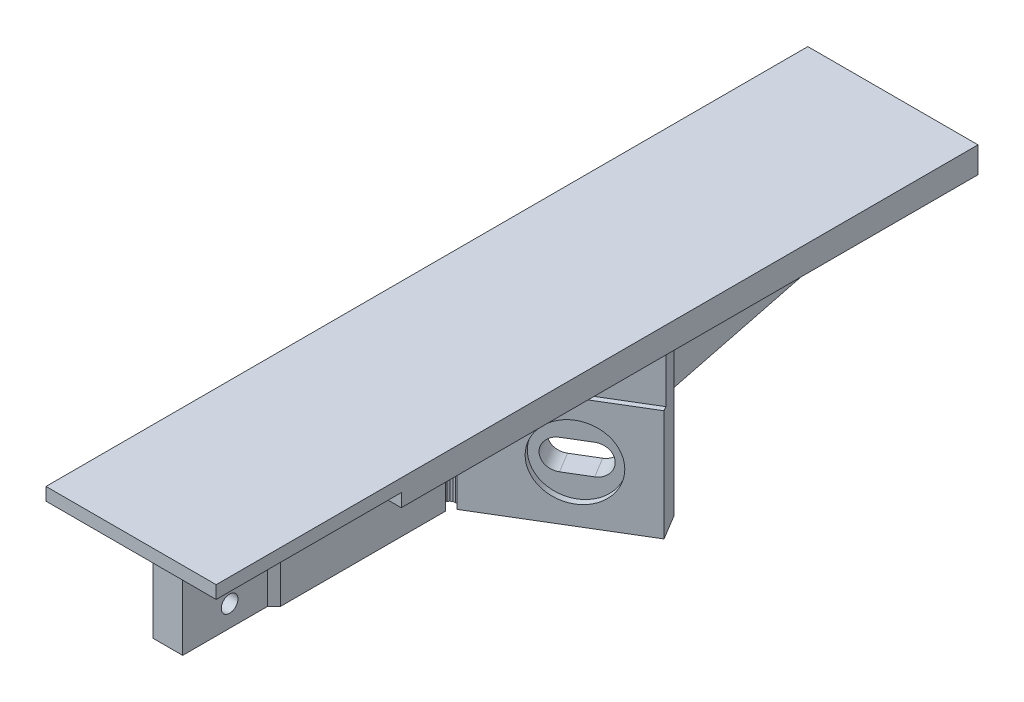
SolidWorks part; units mm, degrees
ref_plane "Front Plane" through (0, 0, 0) normal (0, 0, 1) x (1, 0, 0)
ref_plane "Top Plane" through (0, 0, 0) normal (0, 1, 0) x (1, 0, 0)
ref_plane "Right Plane" through (0, 0, 0) normal (1, 0, 0) x (0, 0, -1)
ref_plane "PY -20.700" through (0, -20.7, 0) normal (0, 1, 0) x (1, 0, 0)
sketch "leg and pad sketch" plane through (0, -20.7, 0) normal (0, 1, 0) x (1, 0, 0)
  line L0 (0.5513, 30.3327) -> (0.3673, 30.8194)
  line L1 (0.3673, 30.8194) -> (0.028, 31.2139)
  line L2 (0.028, 31.2139) -> (-0.4256, 31.4688)
  line L3 (-0.4256, 31.4688) -> (-0.939, 31.5534)
  line L4 (-0.939, 31.5534) -> (-1.4504, 31.4576)
  line L5 (-1.4504, 31.4576) -> (-1.8983, 31.1928)
  line L6 (-1.8983, 31.1928) -> (-2.2288, 30.7909)
  line L7 (-2.2288, 30.7909) -> (-2.4021, 30.3003)
  line L8 (-2.4021, 30.3003) -> (-2.3973, 29.78)
  line L9 (-2.3973, 29.78) -> (-2.2152, 29.2926)
  line L10 (-2.2152, 29.2926) -> (-1.8775, 28.8968)
  line L11 (-1.8775, 28.8968) -> (-1.4248, 28.6402)
  line L12 (-1.4248, 28.6402) -> (-0.9118, 28.5536)
  line L13 (-0.9118, 28.5536) -> (-0.4, 28.6475)
  line L14 (-0.4, 28.6475) -> (-0.4, -9.98)
  line L15 (-0.4, -9.98) -> (-1.92, -11.5)
  line L16 (-1.92, -11.5) -> (-1.92, -31.37)
  line L17 (-1.92, -31.37) -> (-8.92, -31.37)
  line L18 (-8.92, -31.37) -> (-8.92, 32.7926)
  line L19 (-8.92, 32.7926) -> (27.2048, 54.5947)
  line L20 (27.2048, 54.5947) -> (30.8218, 48.6015)
  line L21 (30.8218, 48.6015) -> (0.5513, 30.3327)
extrude "leg and pad" add sketch "leg and pad sketch" along normal mid plane 26
ref_plane "PX -1.350" through (-1.35, 0, 0) normal (1, 0, 0) x (0, 0, -1)
sketch "screw head relief sketch" plane through (-1.35, 0, 0) normal (1, 0, 0) x (0, 0, -1)
  line L0 (23.4, -12.7) -> (23.4, -6.7)
  line L1 (23.4, -6.7) -> (9.4, -6.7)
  line L2 (9.4, -6.7) -> (9.4, -12.7)
  line L3 (9.4, -12.7) -> (23.4, -12.7)
extrude "screw head relief" cut sketch "screw head relief sketch" against normal mid plane 4.7
sketch "insert flange relief sketch" plane through (0, -20.7, 0) normal (0, 1, 0) x (1, 0, 0)
  line L0 (18.3249, 39.8914) -> (17.0331, 42.0318)
  line L1 (17.0331, 42.0318) -> (9.7557, 37.6398)
  line L2 (9.7557, 37.6398) -> (11.0475, 35.4994)
  line L3 (11.0475, 35.4994) -> (18.3249, 39.8914)
revolve "insert flange relief" cut sketch "insert flange relief sketch" angle 360 about L0
sketch "M6 slot end 1 sketch" plane through (0, -20.7, 0) normal (0, 1, 0) x (1, 0, 0)
  line L0 (20.8933, 41.4415) -> (16.243, 49.147)
  line L1 (16.243, 49.147) -> (13.2464, 47.3385)
  line L2 (13.2464, 47.3385) -> (17.8968, 39.633)
  line L3 (17.8968, 39.633) -> (20.8933, 41.4415)
revolve "M6 slot end 1" cut sketch "M6 slot end 1 sketch" angle 360 about L0
sketch "M6 slot end 2 sketch" plane through (0, -20.7, 0) normal (0, 1, 0) x (1, 0, 0)
  line L0 (15.7564, 38.3413) -> (11.106, 46.0467)
  line L1 (11.106, 46.0467) -> (8.1094, 44.2382)
  line L2 (8.1094, 44.2382) -> (12.7598, 36.5328)
  line L3 (12.7598, 36.5328) -> (15.7564, 38.3413)
revolve "M6 slot end 2" cut sketch "M6 slot end 2 sketch" angle 360 about L0
sketch "M6 slot middle sketch" plane through (0, -20.7, 0) normal (0, 1, 0) x (1, 0, 0)
  line L0 (15.7564, 38.3413) -> (20.8933, 41.4415)
  line L1 (20.8933, 41.4415) -> (16.243, 49.147)
  line L2 (16.243, 49.147) -> (11.106, 46.0467)
  line L3 (11.106, 46.0467) -> (15.7564, 38.3413)
extrude "M6 slot middle" cut sketch "M6 slot middle sketch" against normal mid plane 7
ref_plane "PX -5.420" through (-5.42, 0, 0) normal (1, 0, 0) x (0, 0, -1)
sketch "screw holes sketch" plane through (-5.42, 0, 0) normal (1, 0, 0) x (0, 0, -1)
  circle A0 centre (-20.375, -28.7) radius 1.95
  circle A1 centre (-20.375, -12.7) radius 1.95
extrude "screw holes" cut sketch "screw holes sketch" against normal mid plane 9
ref_plane "PY -2.100" through (0, -2.1, 0) normal (0, 1, 0) x (1, 0, 0)
sketch "foot leg sketch" plane through (0, -2.1, 0) normal (0, 1, 0) x (1, 0, 0)
  line L0 (-2.3, 30.0135) -> (-2.3, -9.98)
  line L1 (-2.3, -9.98) -> (-8.92, -9.98)
  line L2 (-8.92, -9.98) -> (-8.92, 32.7926)
  line L3 (-8.92, 32.7926) -> (27.2048, 54.5947)
  line L4 (27.2048, 54.5947) -> (30.2017, 49.6289)
  line L5 (30.2017, 49.6289) -> (-2.3, 30.0135)
extrude "foot leg" add sketch "foot leg sketch" along normal mid plane 12.2
ref_plane "PY 6.535" through (0, 6.535, 0) normal (0, 1, 0) x (1, 0, 0)
sketch "sole under the housing sketch" plane through (0, 6.535, 0) normal (0, 1, 0) x (1, 0, 0)
  line L0 (30.9218, 122) -> (-8.92, 122)
  line L1 (-8.92, 122) -> (-8.92, -13.03)
  line L2 (-8.92, -13.03) -> (30.9218, -13.03)
  line L3 (30.9218, -13.03) -> (30.9218, 122)
extrude "sole under the housing" add sketch "sole under the housing sketch" along normal mid plane 6.07
ref_plane "PY 8.070" through (0, 8.07, 0) normal (0, 1, 0) x (1, 0, 0)
sketch "sole under the block sketch" plane through (0, 8.07, 0) normal (0, 1, 0) x (1, 0, 0)
  line L0 (30.9218, -12.53) -> (-8.92, -12.53)
  line L1 (-8.92, -12.53) -> (-8.92, -56.37)
  line L2 (-8.92, -56.37) -> (30.9218, -56.37)
  line L3 (30.9218, -56.37) -> (30.9218, -12.53)
extrude "sole under the block" add sketch "sole under the block sketch" along normal mid plane 3
ref_plane "PX -6.370" through (-6.37, 0, 0) normal (1, 0, 0) x (0, 0, -1)
sketch "seat gusset sketch" plane through (-6.37, 0, 0) normal (1, 0, 0) x (0, 0, -1)
  line L0 (-9.48, -8.2) -> (-31.37, -8.2)
  line L1 (-31.37, -8.2) -> (-31.37, -7.7)
  line L2 (-31.37, -7.7) -> (-17.1, 7.07)
  line L3 (-17.1, 7.07) -> (-9.48, 7.07)
  line L4 (-9.48, 7.07) -> (-9.48, -8.2)
extrude "seat gusset" add sketch "seat gusset sketch" along normal mid plane 5.1
ref_plane "PX 19.922" through (19.9218, 0, 0) normal (1, 0, 0) x (0, 0, -1)
sketch "tail rib sketch" plane through (19.9218, 0, 0) normal (1, 0, 0) x (0, 0, -1)
  line L0 (53.1, 4) -> (53.1, -12.5)
  line L1 (53.1, -12.5) -> (57.1, -12.5)
  line L2 (57.1, -12.5) -> (120, 3.5)
  line L3 (120, 3.5) -> (120, 4)
  line L4 (120, 4) -> (53.1, 4)
extrude "tail rib" add sketch "tail rib sketch" along normal mid plane 6
sketch "screw head relief to the end sketch" plane through (-1.35, 0, 0) normal (1, 0, 0) x (0, 0, -1)
  line L0 (23.4, -12.7) -> (23.4, 3.3)
  line L1 (23.4, 3.3) -> (9.4, 3.3)
  line L2 (9.4, 3.3) -> (9.4, -12.7)
  line L3 (9.4, -12.7) -> (23.4, -12.7)
extrude "screw head relief to the end" cut sketch "screw head relief to the end sketch" against normal mid plane 4.7
equation "\"diffL\" = 608.8mm"
equation "\"diffW\" = 329.4mm"
equation "\"diffT\" = 2.9mm"
equation "\"chanSlotW\" = 12.9mm"
equation "\"chanSlotDepth\" = 11.13mm"
equation "\"chanFloor\" = 1.57mm"
equation "\"chanLeg\" = 12.7mm"
equation "\"lightL\" = 604.8mm"
equation "\"lightW\" = 330.2mm"
equation "\"lightH\" = 92mm"
equation "\"lightSideFlat\" = 30mm"
equation "\"lightSlopeLen\" = 38.9mm"
equation "\"lightWingDepth\" = 50.1mm"
equation "\"lightWingFlat\" = 90.2mm"
equation "\"lightChanW\" = 99.6mm"
equation "\"lightChanStand\" = 44.1mm"
equation "\"insFlangeD\" = 12.3mm"
equation "\"insFromEnd\" = 20.7mm"
equation "\"insUpSlope\" = 20.8mm"
equation "\"gaugeH\" = 10mm"
equation "\"gaugeStepLen\" = 14mm"
equation "\"gaugeStepW0\" = 13.1mm"
equation "\"gaugeStepDW\" = 0.2mm"
equation "\"gaugeSteps\" = 5mm"
equation "\"gaugeHandleLen\" = 30mm"
equation "\"gaugeHandleW\" = 24mm"
equation "\"gaugeSlot0\" = 3mm"
equation "\"gaugeSlotD\" = 0.1mm"
equation "\"gaugeSlotDepth\" = 8mm"
equation "\"gap\" = 25.4mm"
equation "\"edgeL\" = 1mm"
equation "\"edgeW\" = 0.75mm"
equation "\"proud\" = 1.5mm"
equation "\"seatClr\" = 0.15mm"
equation "\"tongueClrZ\" = 0.1mm"
equation "\"tongueClrX\" = 0.25mm"
equation "\"tongueLen\" = 30mm"
equation "\"armSide\" = 45mm"
equation "\"armEnd\" = 20mm"
equation "\"cornerCham\" = 3mm"
equation "\"brkW\" = 26mm"
equation "\"brkT\" = 7mm"
equation "\"brkSeatClr\" = 0.3mm"
equation "\"brkScrewSpan\" = 16mm"
equation "\"pilotD\" = 2.7mm"
equation "\"pilotDepth\" = 10mm"
equation "\"screwClrD\" = 3.9mm"
equation "\"jogBelow\" = 4mm"
equation "\"padT\" = 7mm"
equation "\"padLen\" = 36mm"
equation "\"m6Clr\" = 7mm"
equation "\"m6Slot\" = 6mm"
equation "\"flangeRelD\" = 17mm"
equation "\"flangeRelDepth\" = 1.5mm"
equation "\"relLen\" = 5mm"
equation "\"relDepth\" = 3.3mm"
equation "\"knockN\" = 100mm"
equation "\"petgcfE\" = 3000mm"
equation "\"mockExtent\" = 110mm"
equation "\"relZnear\" = 9.4mm"
equation "\"relZfar\" = 23.4mm"
equation "\"headD\" = 8mm"
equation "\"headH\" = 2.5mm"
equation "\"headFromEnd\" = 6.8mm"
equation "\"headBack\" = 16.4mm"
equation "\"sideClr\" = 0.4mm"
equation "\"cornerRelR\" = 1.5mm"
equation "\"cornerRelBack\" = 0.6mm"
equation "\"endHeadH\" = 2.8mm"
equation "\"footClr\" = 1.2mm"
equation "\"footEndClr\" = 3.5mm"
equation "\"footLift\" = 3.5mm"
equation "\"footBlockClr\" = 0.5mm"
equation "\"footBack\" = 30mm"
equation "\"footFwd\" = 25mm"
equation "\"footRibH\" = 16mm"
equation "\"footRibT\" = 6mm"
